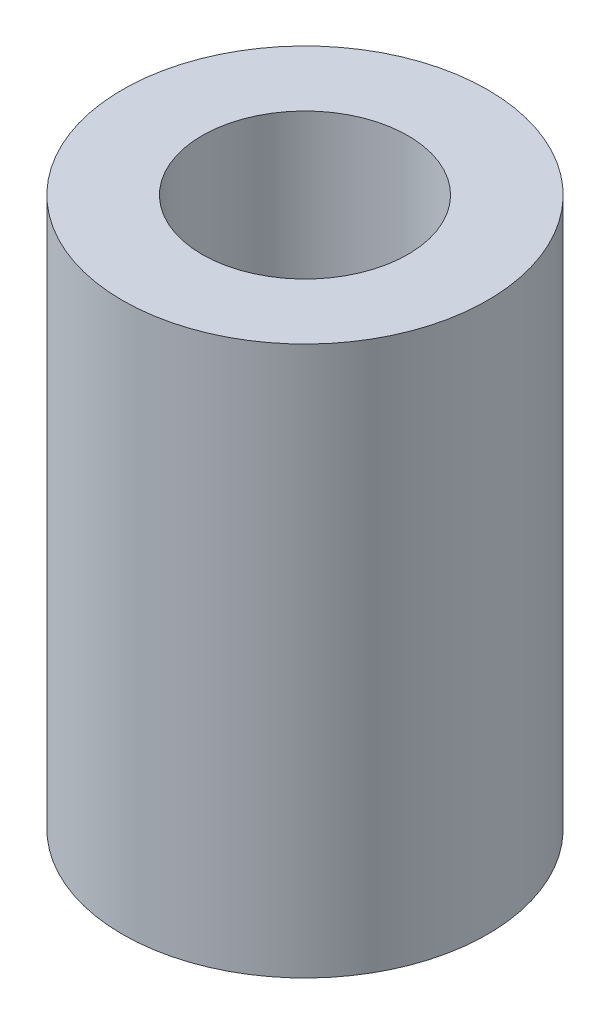
SolidWorks part; units mm, degrees
ref_plane "Front Plane" through (0, 0, 0) normal (0, 0, 1) x (1, 0, 0)
ref_plane "Top Plane" through (0, 0, 0) normal (0, 1, 0) x (1, 0, 0)
ref_plane "Right Plane" through (0, 0, 0) normal (1, 0, 0) x (0, 0, -1)
sketch "Sketch1" plane through (0, 0, 0) normal (0, 1, 0) x (1, 0, 0)
  circle A0 centre (0, 0) radius 1.5
  circle A1 centre (0, 0) radius 2.66
  point P5 (0, 0)
  dimension "D1" = 3
  dimension "D2" = 5.32
extrude "Boss-Extrude1" add sketch "Sketch1" along normal blind 8
